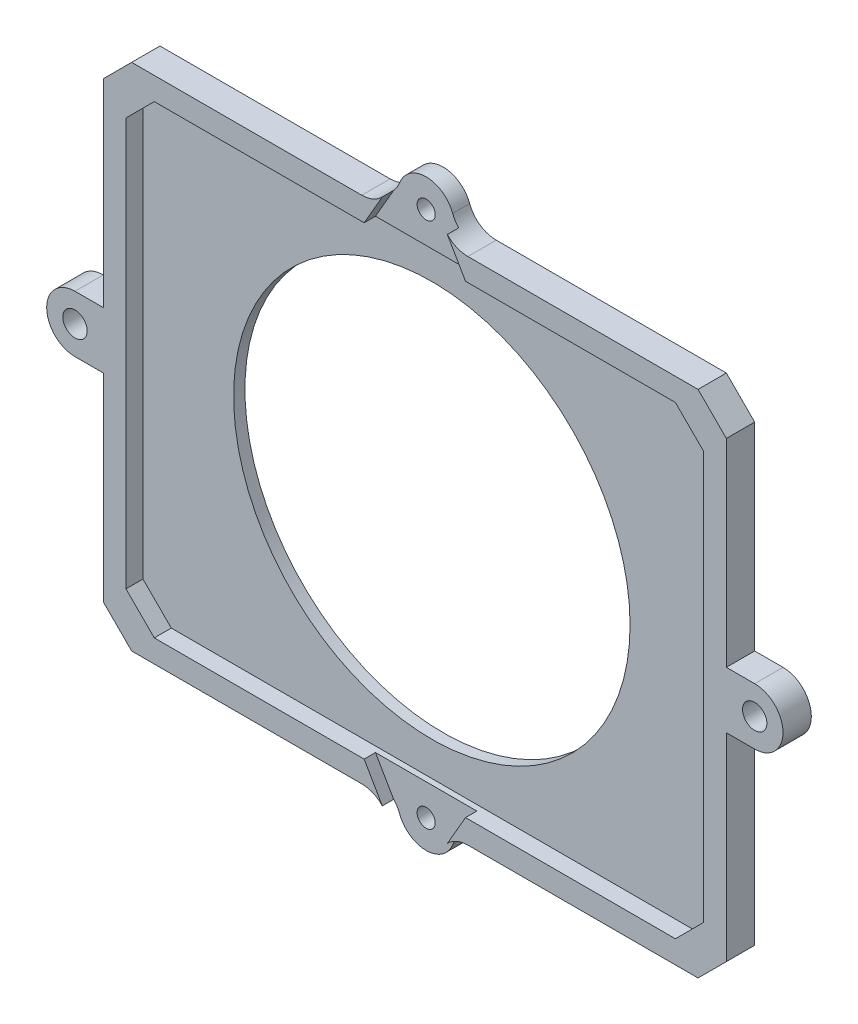
SolidWorks part; units mm, degrees
ref_plane "前视基准面" through (0, 0, 0) normal (0, 0, 1) x (1, 0, 0)
ref_plane "上视基准面" through (0, 0, 0) normal (0, 1, 0) x (1, 0, 0)
ref_plane "右视基准面" through (0, 0, 0) normal (1, 0, 0) x (0, 0, -1)
sketch "草图1" plane through (0, 0, 0) normal (0, 0, 1) x (1, 0, 0)
  line L0 (-1, 81) -> (101, 81)
  line L1 (0, 0) -> (100, 0) construction
  line L2 (0, 0) -> (0, 80) construction
  line L3 (0, 80) -> (100, 80) construction
  line L4 (100, 0) -> (100, 80) construction
  line L5 (0, 0) -> (100, 80) construction
  line L6 (0, 80) -> (100, 0) construction
  line L7 (101, -1) -> (101, 81)
  line L8 (-1, -1) -> (101, -1)
  line L9 (-1, -1) -> (-1, 81)
  circle A0 centre (50, 40) radius 35
  point P4 (50, 40)
  dimension "D4" = 70
  dimension "D1" = 80
  dimension "D2" = 100
  dimension "D3" = 1
extrude "凸台-拉伸1" add sketch "草图1" along normal blind 2
sketch "草图2" plane through (0, 0, 0) normal (0, 0, -1) x (-1, 0, 0)
  line L0 (5, -5) -> (5, 85)
  line L1 (5, 85) -> (-105, 85)
  line L2 (-105, 85) -> (-105, -5)
  line L3 (-105, -5) -> (5, -5)
  line L4 (1, -1) -> (1, 81)
  line L5 (1, 81) -> (-101, 81)
  line L6 (-101, 81) -> (-101, -1)
  line L7 (-101, -1) -> (1, -1)
  line L8 (1, -1) -> (1, 81)
  line L9 (1, 81) -> (-101, 81)
  line L10 (-101, 81) -> (-101, -1)
  line L11 (-101, -1) -> (1, -1)
  dimension "D1" = 0
  dimension "D2" = 4
extrude "凸台-拉伸2" add sketch "草图2" against normal blind 5
sketch "草图3" plane through (0, 0, 0) normal (0, 0, -1) x (-1, 0, 0)
  line L0 (-50, 86.5) -> (-50, -6.5) construction
  line L1 (-55, 86.5) -> (-55, 85)
  line L2 (5, 85) -> (-105, 85) construction
  line L3 (-45, 86.5) -> (-45, 85)
  line L4 (-55, 85) -> (-50.5568, 85)
  line L5 (-55, -6.5) -> (-55, -5)
  line L6 (-105, -5) -> (5, -5) construction
  line L8 (-55, -5) -> (-50.5568, -5)
  line L9 (-45, -6.5) -> (-45, -5)
  line L10 (-49.4432, -5) -> (-45, -5)
  line L11 (-49.4432, 85) -> (-45, 85)
  arc A0 (-49.4432, 85) -> (-50.5568, 85) centre (-50, 86.5) ccw
  arc A1 (-50.5568, -5) -> (-49.4432, -5) centre (-50, -6.5) ccw
  circle A2 centre (-50, 40) radius 35 construction
  arc A3 (-45, 86.5) -> (-55, 86.5) centre (-50, 86.5) ccw
  arc A4 (-55, -6.5) -> (-45, -6.5) centre (-50, -6.5) ccw
  point P4 (-50, 40)
  dimension "D1" = 3.2
  dimension "D3" = 10
  dimension "D2" = 93
extrude "凸台-拉伸3" add sketch "草图3" against normal offset from surface (3 mm away) 1 up to face at (50, 40, 2) offset beyond the face yes
sketch "草图4" plane through (0, 0, 3) normal (0, 0, 1) x (1, 0, 0)
  line L0 (-1, 40) -> (101, 40) construction
  line L1 (-1, 81) -> (-1, -1) construction
  line L2 (101, 81) -> (101, -1) construction
  line L3 (45.6699, 89) -> (41.0511, 81)
  line L4 (101, 81) -> (-1, 81) construction
  line L5 (41.0511, 81) -> (58.9489, 81)
  line L6 (58.9489, 81) -> (54.3301, 89)
  line L7 (58.9489, -1) -> (54.3301, -9)
  line L8 (41.0511, -1) -> (58.9489, -1)
  line L9 (45.6699, -9) -> (41.0511, -1)
  arc A2 (55, 86.5) -> (45, 86.5) centre (50, 86.5) ccw construction
  arc A3 (54.3301, 89) -> (45.6699, 89) centre (50, 86.5) ccw
  arc A4 (54.3301, -9) -> (45.6699, -9) centre (50, -6.5) cw
  dimension "D1" = 60
  dimension "D2" = 60
extrude "切除-拉伸1" cut sketch "草图4" along normal through all
fillet "圆角1" radius 5 4 edges at (55, -5, 1.5) (45, -5, 1.5) (55, 85, 1.5) (45, 85, 1.5)
sketch "草图5" plane through (0, 0, 5) normal (0, 0, 1) x (1, 0, 0)
  line L0 (50, 86.5) -> (50, -6.5) construction
  line L1 (110, 40) -> (-10, 40) construction
  line L2 (-5, -5) -> (-5, 85) construction
  line L3 (-10, 45) -> (-5, 45)
  line L4 (-5, 45) -> (-5, 35)
  line L5 (-5, 35) -> (-10, 35)
  line L6 (105, 35) -> (110, 35)
  line L7 (105, 45) -> (105, 35)
  line L8 (110, 45) -> (105, 45)
  circle A0 centre (-10, 40) radius 2.15
  arc A1 (-10, 45) -> (-10, 35) centre (-10, 40) ccw
  arc A2 (110, 45) -> (110, 35) centre (110, 40) cw
  circle A3 centre (110, 40) radius 2.15
  point P14 (50, 40)
  dimension "D1" = 4.3
  dimension "D2" = 10
extrude "凸台-拉伸4" add sketch "草图5" against normal up to surface (5 mm away) up to face at (50, -6.55, 0)
chamfer "倒角1" distance 5 angle 45 8 edges at (-1, -1, 3.5) (-5, -5, 2.5) (105, -5, 2.5) (101, -1, 3.5) (101, 81, 3.5) (105, 85, 2.5) (-5, 85, 2.5) (-1, 81, 3.5)
sketch "草图6" plane through (0, 0, 3) normal (0, 0, 1) x (1, 0, 0)
  circle A0 centre (50, 86.5) radius 1.6
  circle A1 centre (50, -6.5) radius 1.6
  arc A2 (49.4432, -5) -> (50.5568, -5) centre (50, -6.5) ccw construction
extrude "切除-拉伸2" cut sketch "草图6" against normal through all
